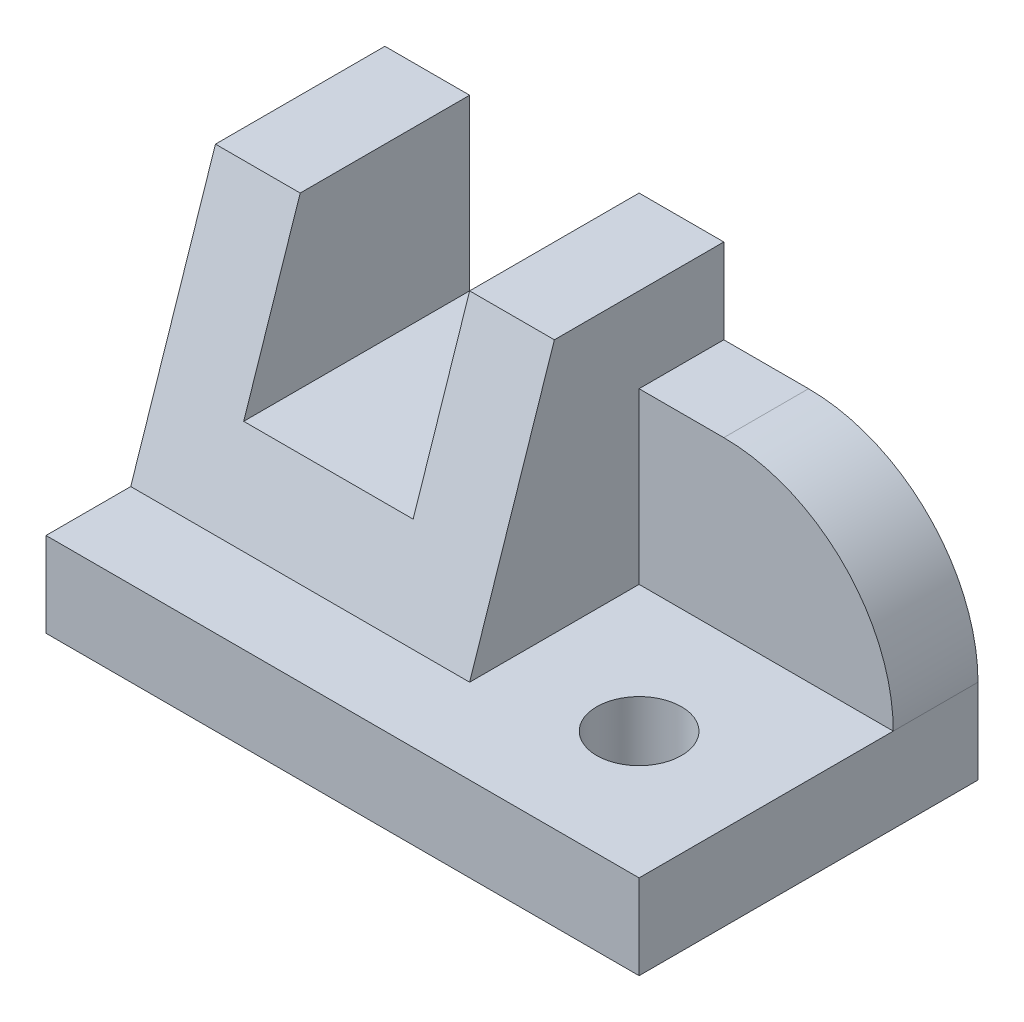
SolidWorks part; units mm, degrees
ref_plane "Front Plane" through (0, 0, 0) normal (0, 0, 1) x (1, 0, 0)
ref_plane "Top Plane" through (0, 0, 0) normal (0, 1, 0) x (1, 0, 0)
ref_plane "Right Plane" through (0, 0, 0) normal (1, 0, 0) x (0, 0, -1)
ref_plane "Plane1" through (0, 0, 0) normal (-1, 0, 0) x (0, -1, 0)
sketch "Sketch1" plane through (0, 0, 0) normal (-1, 0, 0) x (0, -1, 0)
  line L0 (-10, -10) -> (-40, -20)
  line L1 (-40, -20) -> (-10, -20)
  line L2 (-10, -20) -> (-10, -10)
  dimension "D1" = 30
  dimension "Width" = 10
extrude "Boss-Extrude1" add sketch "Sketch1" against normal blind 40
sketch "Sketch2" plane through (0, 0, -20) normal (0, 0, -1) x (-1, 0, 0)
  line L0 (-40, 40) -> (0, 40)
  line L1 (0, 40) -> (0, 10)
  line L2 (0, 10) -> (-40, 10)
  line L3 (-40, 10) -> (-40, 40)
extrude "Boss-Extrude2" add sketch "Sketch2" along normal blind 20
sketch "Sketch3" plane through (40, 0, 0) normal (1, 0, 0) x (0, 0, -1)
  line L0 (40, 10) -> (0, 10)
  line L1 (0, 10) -> (20, 40)
  line L2 (20, 40) -> (40, 40)
  line L3 (40, 40) -> (40, 10)
extrude "Boss-Extrude3" add sketch "Sketch3" along normal blind 30
sketch "Sketch4" plane through (70, 0, 0) normal (1, 0, 0) x (0, 0, -1)
  line L0 (20, 40) -> (0, 10)
  line L1 (0, 10) -> (30, 10)
  line L2 (30, 10) -> (30, 30)
  line L3 (30, 30) -> (40, 30)
  line L4 (40, 30) -> (40, 40)
  line L5 (40, 40) -> (20, 40)
extrude "Cut-Extrude1" cut sketch "Sketch4" against normal blind 30
sketch "Sketch5" plane through (0, 10, 0) normal (0, -1, 0) x (1, 0, 0)
  line L0 (70, 0) -> (70, -40)
  line L1 (70, -40) -> (0, -40)
  line L2 (0, -40) -> (0, 0)
  line L3 (0, 0) -> (70, 0)
extrude "Boss-Extrude4" add sketch "Sketch5" along normal blind 10
sketch "Sketch6" plane through (0, 0, -40) normal (0, 0, -1) x (-1, 0, 0)
  line L0 (-30, 40) -> (-30, 20)
  line L1 (-30, 20) -> (-10, 20)
  line L2 (-10, 20) -> (-10, 40)
  line L3 (-10, 40) -> (-30, 40)
extrude "Cut-Extrude2" cut sketch "Sketch6" against normal through all
hole_wizard "Ø10.0 (10) Diameter Hole1" positions "Sketch8" profile "Sketch7" hole size "Ø10.0" standard "ANSI Metric"
sketch "Sketch8" plane through (0, 0, 0) normal (0, -1, 0) x (-1, 0, 0)
  point P0 (-55, 15)
sketch "Sketch7" plane through (55, 0, -15) normal (1, 0, 0) x (0, 0, -1)
  line L0 (0, 0) -> (0, 40)
  line L1 (0, 40) -> (5, 40)
  line L2 (5, 40) -> (5, 0)
  line L5 (5, 0) -> (0, 0)
  line L11 (0, -6.35) -> (0, 107.95) construction
  dimension "Thru Hole Dia." = 10
  dimension "Thru Hole Depth" = 40
fillet "Fillet1" radius 20 1 edges at (70, 30, -35) tangent propagation no
